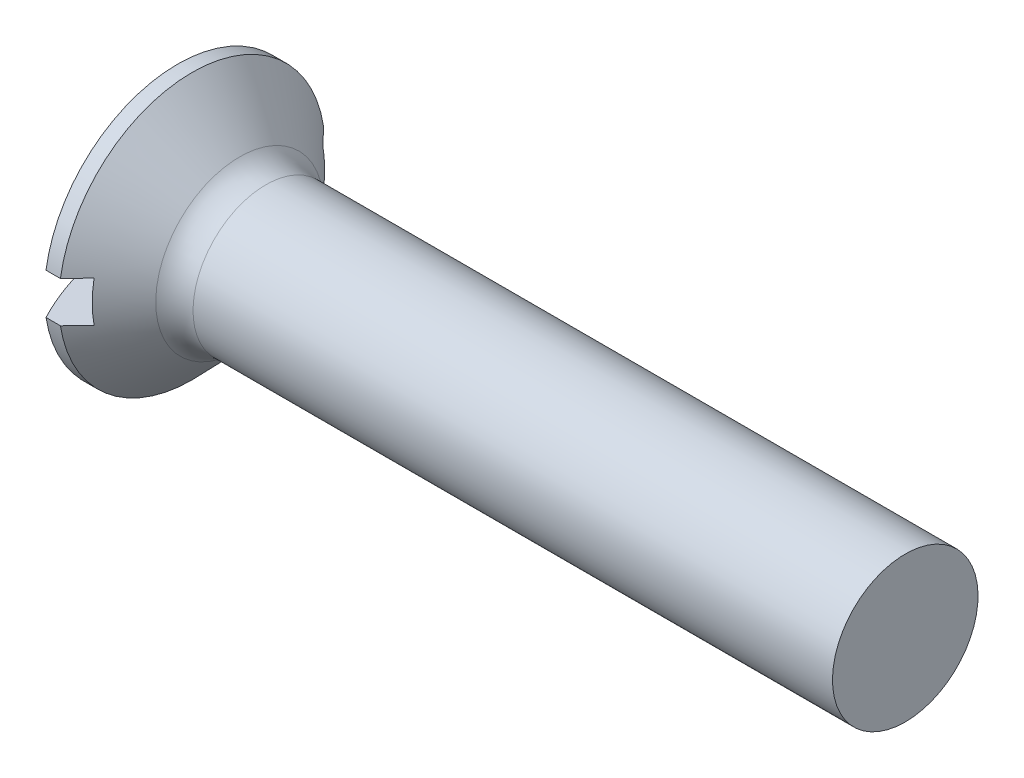
SolidWorks part; units mm, degrees
ref_plane "Front Plane" through (0, 0, 0) normal (0, 0, 1) x (1, 0, 0)
ref_plane "Top Plane" through (0, 0, 0) normal (0, 1, 0) x (1, 0, 0)
ref_plane "Right Plane" through (0, 0, 0) normal (1, 0, 0) x (0, 0, -1)
sketch "BodySke" plane through (0, 0, 0) normal (0, 0, 1) x (1, 0, 0)
  line L0 (2.28, 0) -> (111.3824, 0) construction
  line L1 (2.28, 0) -> (2.28, 9.15) construction
  line L2 (2.28, 9.15) -> (3.2724, 9.15)
  line L3 (3.2724, 9.15) -> (7.28, 5)
  line L4 (7.28, 5) -> (52.28, 5)
  line L5 (52.28, 5) -> (52.28, 0)
  line L6 (8.78, 8.824) -> (8.78, -5.8939) construction
  line L7 (2.28, 0) -> (52.28, 0)
  line L8 (10.28, 8.824) -> (10.28, -4.958) construction
  line L9 (2.28, -9.15) -> (3.2724, -9.15) construction
  line L10 (3.2724, -9.15) -> (7.28, -5) construction
  line L11 (7.28, -5) -> (52.28, -5) construction
  line L12 (2.28, 0) -> (-13.4753, 0) construction
  line L13 (0, 0) -> (0, 11.6167) construction
  line L14 (2.28, 0) -> (0, 0)
  arc A0 (0, 0) -> (2.28, 9.15) centre (19.5, 0) cw
  point P10 (52.28, 4.172)
  dimension "Thread_minor" = 8.344
  dimension "Length" = 50
  dimension "Head_height" = 5
  dimension "Head_dia" = 18.3
  dimension "Advance" = 1.5
revolve "BaseBody" add sketch "BodySke" angle 360 about L0
cosmetic thread "ThreadCosmetic" [suppressed] parameters "Thread_minor"=8.344
fillet "Fillet1" radius 2.5 1 edges at (7.28, -5, 0)
sketch "SlotSke" plane through (0, 0, 0) normal (1, 0, 0) x (0, 0, -1)
  line L1 (-9.15, 1.405) -> (9.15, 1.405)
  line L2 (-9.15, 1.405) -> (-9.15, -1.405)
  line L3 (-9.15, -1.405) -> (9.15, -1.405)
  line L4 (9.15, 1.405) -> (9.15, -1.405)
  dimension "D1" = 18.3
  dimension "D2" = 9.15
  dimension "D3" = 1.405
extrude "Slot" cut sketch "SlotSke" along normal blind 4.4
sketch "ThdSchSke" plane through (0, 0, 0) normal (0, 0, 1) x (1, 0, 0)
  line L0 (0, 0) -> (55.1256, 0) construction
  line L1 (2.28, 0) -> (111.3824, 0) construction
  line L2 (51.802, 5) -> (51.802, 5.9561)
  line L3 (51.802, 5.9561) -> (52.7581, 5.9561)
  line L4 (52.7581, 5.9561) -> (52.7581, 5)
  line L5 (52.7581, 5) -> (52.28, 4.172)
  line L6 (52.28, 4.172) -> (51.802, 5)
  line L7 (7.28, 5) -> (52.28, 5) construction
  line L13 (52.28, 5) -> (52.28, 0) construction
revolve "ThreadSchematic" [suppressed] cut sketch "ThdSchSke" angle 360 about L0
pattern_linear "ThdSchPat" [suppressed] count 29 along (-1, 0, 0) of bodies 103
equation "\"Thread_minor@ThreadCosmetic\" = \"Thread_minor@BodySke\""
equation "\"D1@SlotSke\" = \"Head_dia@BodySke\""
equation "\"D2@SlotSke\" = \"D1@SlotSke\" / 2"
equation "\"D3@SlotSke\" = \"Slot_width@SlotSke\" / 2"
equation "\"Advance@ThdSchPat\" = \"Advance@BodySke\""
equation "\"D1@ThdSchPat\" =  int( (  \"Length@BodySke\"-\"Head_height@BodySke\"-\"Tread_runout@BodySke\" )  / \"Advance@ThdSchPat\" )+1 "
